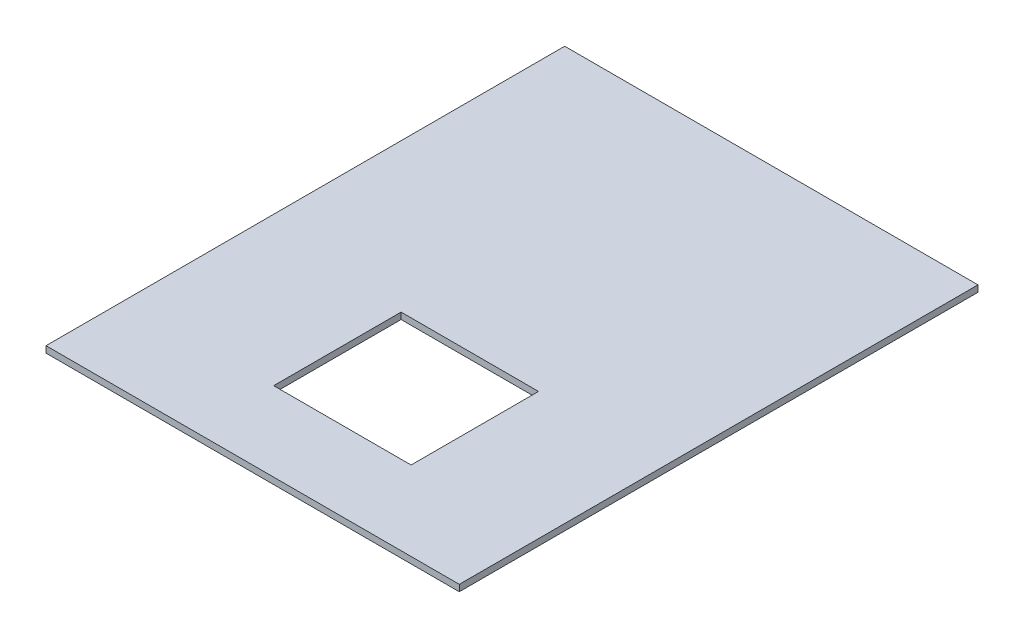
SolidWorks part; units mm, degrees
material "6061-T6 (SS)"
ref_plane "Front" through (0, 0, 0) normal (0, 0, 1) x (1, 0, 0)
ref_plane "Top" through (0, 0, 0) normal (0, 1, 0) x (1, 0, 0)
ref_plane "Right" through (0, 0, 0) normal (1, 0, 0) x (0, 0, -1)
ref_axis "side-side" through (80.9, 0, 0) along (-1, 0, 0)
ref_axis "up-down" through (0, 50, 0) along (0, -1, 0)
ref_axis "front-back" through (0, 0, -80.9) along (0, 0, 1)
sketch "Sketch1" plane through (0, 0, 0) normal (0, 1, 0) x (1, 0, 0)
  line L0 (-152.4, 191.262) -> (152.4, -191.262) construction
  line L1 (-152.4, 191.262) -> (152.4, 191.262)
  line L2 (-152.4, 191.262) -> (-152.4, -191.262)
  line L3 (-152.4, -191.262) -> (152.4, -191.262)
  line L4 (152.4, 191.262) -> (152.4, -191.262)
  line L6 (-42.926, -38.862) -> (58.42, -38.862)
  line L7 (-42.926, -38.862) -> (-42.926, -132.842)
  line L8 (-42.926, -132.842) -> (58.42, -132.842)
  line L9 (58.42, -38.862) -> (58.42, -132.842)
  dimension "D1" = 304.8
  dimension "D2" = 382.524
  dimension "D3" = 93.98
  dimension "D4" = 109.474
  dimension "D5" = 58.42
  dimension "D6" = 93.98
extrude "Boss-Extrude1" add sketch "Sketch1" along normal blind 4.7625
